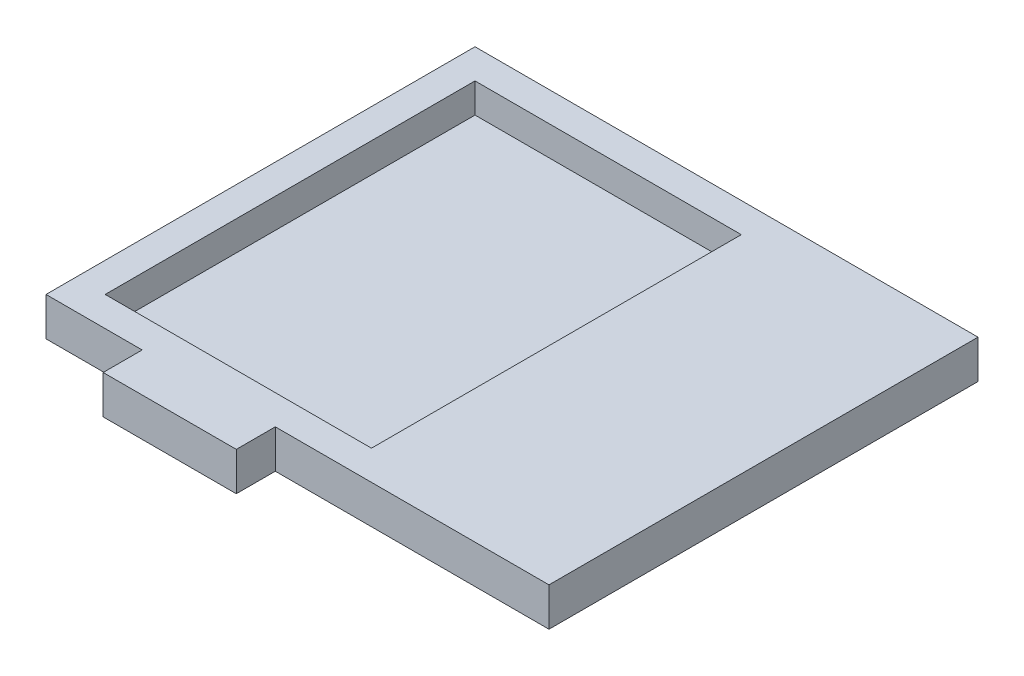
SolidWorks part; units mm, degrees
material "Natural Rubber"
ref_plane "Front Plane" through (0, 0, 0) normal (0, 0, 1) x (1, 0, 0)
ref_plane "Top Plane" through (0, 0, 0) normal (0, 1, 0) x (1, 0, 0)
ref_plane "Right Plane" through (0, 0, 0) normal (1, 0, 0) x (0, 0, -1)
sketch "Sketch1" plane through (0, 0, 0) normal (0, 1, 0) x (1, 0, 0)
  line L0 (45, 0) -> (45, -23.1837) construction
  line L1 (0, 0) -> (90, 0)
  line L2 (0, 0) -> (0, 125)
  line L3 (0, 125) -> (90, 125)
  line L4 (90, 0) -> (90, 125)
  line L5 (-10, -10) -> (160, -10)
  line L6 (-10, -10) -> (-10, 135)
  line L7 (-10, 135) -> (160, 135)
  line L8 (160, -10) -> (160, 135)
  line L9 (22.5, -10) -> (67.5, -10)
  line L10 (22.5, -10) -> (22.5, -23.1837)
  line L11 (22.5, -23.1837) -> (67.5, -23.1837)
  line L12 (67.5, -10) -> (67.5, -23.1837)
  point P16 (45, -23.1837)
  dimension "D1" = 90
  dimension "D2" = 125
  dimension "D3" = 10
  dimension "D4" = 10
  dimension "D5" = 70
  dimension "D6" = 10
  dimension "D7" = 45
extrude "Boss-Extrude1" add sketch "Sketch1" against normal blind 3 contours L1 L4 L3 L2 | L5 L8 L7 L6 L4 L1 L2 L3 | L2 L1 L4 L3 | L6 L5 L8 L7 | L10 L9 L12 L11 region at (45, 0, -62.5) region at (100.1866, 0, -62.5)
extrude "Boss-Extrude2" add sketch "Sketch1<3>" along normal blind 10 contours L4 L1 L9 L5 L8 L7 L6 L2 L3 | L0 L5 L10 L11 | L9 L0 L11 L12 region at (100.1866, 0, -62.5) region at (56.25, 0, 16.5918) region at (33.75, 0, 16.5918)
sketch "Sketch1<3>" plane through (0, 0, 0) normal (0, 1, 0) x (1, 0, 0) same geometry as "Sketch1"
